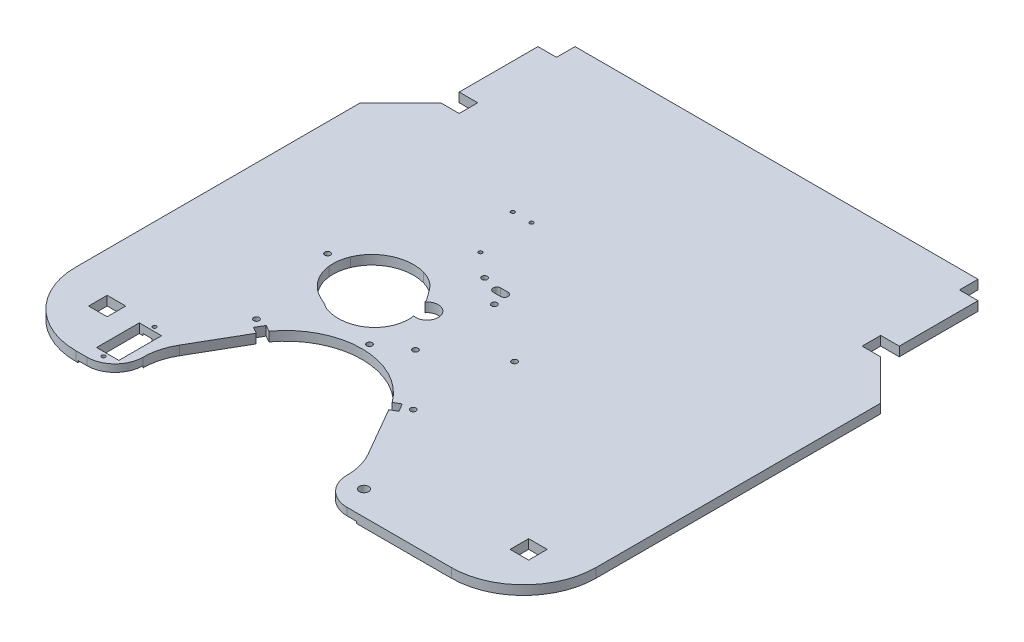
SolidWorks part; units mm, degrees
material "ABS PC"
ref_plane "Plan de face" through (0, 0, 0) normal (0, 0, 1) x (1, 0, 0)
ref_plane "Plan de dessus" through (0, 0, 0) normal (0, 1, 0) x (1, 0, 0)
ref_plane "Plan de droite" through (0, 0, 0) normal (1, 0, 0) x (0, 0, -1)
sketch "Esquisse1" plane through (0, 0, 0) normal (0, 1, 0) x (1, 0, 0)
  line L1 (-140.1, 31.2) -> (140.1, 31.2)
  line L2 (-140.1, 31.2) -> (-140.1, -245.0829)
  line L3 (-140.1, -245.0829) -> (140.1, -245.0829)
  line L4 (140.1, 31.2) -> (140.1, -245.0829)
  line L5 (45, -245.0829) -> (50, -245.0829) construction
  line L6 (-113.5, 31.2) -> (113.5, 31.2) construction
  line L7 (140.1, -4) -> (140.1, 4) construction
  line L8 (-140.1, 4) -> (-140.1, -4) construction
extrude "Boss.-Extru.1" add sketch "Esquisse1" along normal blind 5
sketch "Esquisse2" plane through (0, 0, 0) normal (0, 1, 0) x (1, 0, 0)
  line L3 (-58.1815, -184) -> (-61.6457, -182)
  line L4 (-61.6457, -182) -> (-64.1457, -186.3301)
  line L5 (-64.1457, -186.3301) -> (-60.6815, -188.3301)
  line L7 (-25, -132) -> (-25, -245.0829) construction
  line L8 (-58.1815, -184) -> (-60.6815, -188.3301) construction
  line L9 (-62.6323, -132) -> (62.6323, -132) construction
  line L10 (-25, -62.6323) -> (-25, 62.6323) construction
  line L11 (-60.6815, -188.3301) -> (-75.8539, -214.6094)
  line L13 (-58.1815, -184) -> (-54.7174, -186) construction
  line L14 (-25, -168.5125) -> (-25, -231.5125) construction
  line L16 (140.1, -245.0829) -> (-140.1, -245.0829) construction
  line L17 (-140.1, -245.0829) -> (140.1, -245.0829) construction
  line L18 (8.1815, -184) -> (4.7174, -186) construction
  line L20 (8.1815, -184) -> (10.6815, -188.3301) construction
  line L21 (10.6815, -188.3301) -> (25.8539, -214.6094)
  line L22 (14.1457, -186.3301) -> (10.6815, -188.3301)
  line L23 (11.6457, -182) -> (14.1457, -186.3301)
  line L24 (8.1815, -184) -> (11.6457, -182)
  line L25 (-62.8957, -184.1651) -> (-67.2258, -181.6651) construction
  line L26 (-95, -245.0829) -> (45, -245.0829)
  arc A1 (8.1815, -184) -> (-58.1815, -184) centre (-25, -208.0829) ccw
  arc A2 (-95, -245.0829) -> (-80, -230.0829) centre (-95, -230.0829) ccw
  arc A3 (-95, -245.0829) -> (-86.2863, -217.8734) centre (-95, -230.0829) ccw construction
  arc A4 (-80, -230.0829) -> (-75.8539, -214.6094) centre (-49.0531, -230.0829) cw
  arc A5 (30, -230.0829) -> (25.8539, -214.6094) centre (-0.9469, -230.0829) ccw
  arc A6 (45, -245.0829) -> (30, -230.0829) centre (45, -230.0829) cw
  circle A8 centre (-67.2258, -181.6651) radius 1.5
  circle A10 centre (17.2258, -181.6651) radius 1.5
  dimension "D4" = 41
  dimension "D8" = 5
  dimension "D9" = 3
  dimension "D1" = 4
  dimension "D2" = 52
  dimension "D3" = 37
  dimension "D5" = 90
  dimension "D6" = 5
  dimension "D7" = 30
extrude "Enlèv. mat.-Extru.2" cut sketch "Esquisse2" along normal through all
sketch "Esquisse3" plane through (0, 5, 0) normal (0, 1, 0) x (1, 0, 0)
  line L0 (-30.2322, -127.0569) -> (-26.1247, -139.1312)
  spline S0 degree 3 poles (-1524.8341, -1452.5331) (-200.5452, -428.348) (10.8704, -188.1918) (-31.7245, -126.6315) (-31.8941, -126.3945) (-32.4016, -125.6823) (-32.7422, -125.2091) (-58.8228, -89.2587) (-90.5389, -57.2295) (-1659.8243, -1285.8652) knots -31.850463 -31.850463 -31.850463 -31.850463 0.125 0.125 0.25 0.25 0.5 0.5 19.29405 19.29405 19.29405 19.29405 only from (-31.0727, -127.5986) to (-35.1803, -121.9365)
  spline S1 degree 3 poles (364.0931, 1835.8687) (-340.6814, -513.038) (-113.9465, -84.5198) (-40.8811, -117.114) (-40.044, -117.5631) (-38.8602, -118.3319) (-38.4767, -118.6044) (-37.7343, -119.185) (-37.3745, -119.4945) (-14.0434, -142.3698) (-68.5996, -233.8683) (1519.3139, 1134.9781) knots -20.904049 -20.904049 -20.904049 -20.904049 0.25 0.25 0.5 0.5 0.625 0.625 0.75 0.75 9.313235 9.313235 9.313235 9.313235 only from (-44.3577, -115.7789) to (-35.1803, -121.9365)
  spline S2 degree 3 poles (-1305.5548, -1643.1059) (8.9079, -543.4216) (30.3671, -122.9167) (-49.4488, -114.9227) (-50.737, -114.9092) (-52.6603, -115.0546) (-53.2999, -115.1309) (-54.576, -115.34) (-55.2153, -115.474) (-57.0956, -115.9555) (-58.3066, -116.3821) (-60.0589, -117.1815) (-60.6325, -117.4741) (-61.7574, -118.1146) (-62.3096, -118.4643) (-63.8985, -119.5739) (-64.8782, -120.402) (-66.225, -121.7806) (-66.6531, -122.2633) (-67.2625, -123.0236) (-67.4604, -123.2834) (-67.8414, -123.8087) (-68.025, -124.075) (-110.7871, -189.31) (235.2262, -459.8979) (1576.8374, -1257.2957) knots -7.457247 -7.457247 -7.457247 -7.457247 0.125 0.125 0.25 0.25 0.3125 0.3125 0.375 0.375 0.5 0.5 0.5625 0.5625 0.625 0.625 0.75 0.75 0.8125 0.8125 0.84375 0.84375 0.875 0.875 8.398041 8.398041 8.398041 8.398041 only from (-44.3577, -115.7789) to (-70, -127.755)
  spline S3 degree 3 poles (-47.9813, 1856.8275) (125.181, -244.0769) (-72.0855, -184.256) (-71.4642, -134.1161) (-71.4011, -133.3001) (-71.1736, -131.6775) (-71.0075, -130.8697) (-17.8642, 63.8002) (2969.019, -622.8948) (-1651.8454, 973.7425) knots -14.76961 -14.76961 -14.76961 -14.76961 0.25 0.25 0.5 0.5 0.75 0.75 62.135828 62.135828 62.135828 62.135828 only from (-71.343, -137.3985) to (-70, -127.755)
  spline S4 degree 3 poles (-2001.2881, 32.8008) (2629.6596, 821.1196) (-125.1007, 42.2047) (-70.5251, -141.1324) (-70.3458, -141.6526) (-69.9413, -142.6832) (-69.718, -143.1876) (-68.9919, -144.665) (-68.4298, -145.6034) (-67.479, -146.9469) (-67.1435, -147.384) (-66.4359, -148.235) (-66.0677, -148.6441) (-64.924, -149.8269) (-64.1096, -150.5562) (-62.7975, -151.5474) (-62.3475, -151.8633) (-61.6568, -152.3195) (-61.425, -152.47) (-60.9583, -152.7645) (-60.7209, -152.9041) (-60.001, -153.3084) (-59.5102, -153.5575) (-58.5114, -154.0234) (-58.0032, -154.2398) (-57.2409, -154.5624) (-56.9867, -154.6699) (-56.4801, -154.8889) (-56.2268, -154.9985) (-55.7258, -155.2315) (-55.4826, -155.3662) (-43.6824, -163.0213) (-44.4169, -201.2221) (725.64, 1684.5228) knots -21.636057 -21.636057 -21.636057 -21.636057 0.125 0.125 0.1875 0.1875 0.25 0.25 0.375 0.375 0.4375 0.4375 0.5 0.5 0.625 0.625 0.6875 0.6875 0.71875 0.71875 0.75 0.75 0.8125 0.8125 0.875 0.875 0.90625 0.90625 0.9375 0.9375 0.96875 0.96875 2.500832 2.500832 2.500832 2.500832 only from (-71.343, -137.3985) to (-54.5478, -156)
  spline S5 degree 3 poles (-1738.4139, 892.0597) (140.9741, 43.0874) (2.9113, -175.9233) (-52.26, -157.2053) (-52.4819, -157.1257) (-52.8129, -157.0004) (-52.9231, -156.9582) (-53.1393, -156.8624) (-53.2451, -156.8096) (-53.557, -156.6406) (-53.7605, -156.5209) (-66.1987, -148.6858) (-58.0496, -108.9252) (-1163.5294, -1819.9055) knots -30.265211 -30.265211 -30.265211 -30.265211 0.5 0.5 0.625 0.625 0.6875 0.6875 0.75 0.75 0.875 0.875 8.537384 8.537384 8.537384 8.537384 only from (-49.3008, -158) to (-54.5478, -156)
  spline S6 degree 3 poles (-1949.1275, 426.9773) (43.5324, -0.0898) (1.2961, -154.0463) (-44.2435, -158.3269) (-44.8765, -158.3561) (-46.1445, -158.356) (-46.7811, -158.3264) (-118.6227, -151.5571) (-143.9564, 223.9249) (-15.0957, 1838.9163) knots -17.515041 -17.515041 -17.515041 -17.515041 0.25 0.25 0.5 0.5 0.75 0.75 28.888572 28.888572 28.888572 28.888572 only from (-41.7229, -158) to (-49.3008, -158)
  spline S7 degree 3 poles (-1666.5719, -1296.3963) (-65.6297, 95.6251) (7.8642, -129.1094) (-36.0016, -155.9655) (-36.6799, -156.3213) (-38.0707, -156.9471) (-38.7813, -157.2165) (-86.4686, -172.17) (-201.3678, -13.098) (1712.2684, 789.9411) knots -16.36827 -16.36827 -16.36827 -16.36827 0.25 0.25 0.5 0.5 0.75 0.75 16.93969 16.93969 16.93969 16.93969 only from (-33.4851, -154.245) to (-41.7229, -158)
  spline S8 degree 3 poles (1046.2165, -1823.3231) (-784.0739, 385.5367) (-101.1747, -227.9262) (-31.3895, -152.2364) (-31.1171, -151.9192) (-30.5932, -151.2613) (-30.343, -150.9217) (-29.6368, -149.8847) (-29.2193, -149.1653) (-28.6747, -148.043) (-28.5063, -147.6619) (-15.3248, -114.6524) (-97.8799, -22.7511) (-912.2607, -1937.4947) knots -30.529041 -30.529041 -30.529041 -30.529041 0.25 0.25 0.375 0.375 0.5 0.5 0.75 0.75 0.875 0.875 11.380924 11.380924 11.380924 11.380924 only from (-33.4851, -154.245) to (-27.928, -146.0877)
  spline S9 degree 3 poles (-89.1423, -2133.2638) (-210.1557, -2.8223) (-21.556, -93.2311) (-33.3079, -196.0579) (-262.9799, -213.9602) (-2020.0373, 10.4615) knots -20.97712 -20.97712 -20.97712 -20.97712 0.5 0.5 23.678782 23.678782 23.678782 23.678782 only from (-27.1228, -139.1933) to (-27.928, -146.0877)
  spline S10 degree 3 poles (-27.1228, -139.1933) (-27.0502, -140.3605) (-27.0765, -141.534) (-27.3396, -143.8367) (-27.5752, -144.9715) (-27.928, -146.0877) knots 0 0 0 0 0.5 0.5 1 1 1 1 construction
  spline S11 degree 3 poles (-33.4851, -154.245) (-32.8413, -153.7217) (-32.2363, -153.1548) (-31.3895, -152.2364) (-31.1171, -151.9192) (-30.5932, -151.2613) (-30.343, -150.9217) (-29.6368, -149.8847) (-29.2193, -149.1653) (-28.6747, -148.043) (-28.5063, -147.6619) (-28.1963, -146.8857) (-28.0548, -146.4892) (-27.928, -146.0877) knots 0 0 0 0 0.25 0.25 0.375 0.375 0.5 0.5 0.75 0.75 0.875 0.875 1 1 1 1 construction
  spline S12 degree 3 poles (-33.4851, -154.245) (-34.0776, -154.7266) (-34.7013, -155.1695) (-36.0016, -155.9655) (-36.6799, -156.3213) (-38.0707, -156.9471) (-38.7813, -157.2165) (-40.2317, -157.6713) (-40.9731, -157.8572) (-41.7229, -158) knots 0 0 0 0 0.25 0.25 0.5 0.5 0.75 0.75 1 1 1 1 construction
  spline S13 degree 3 poles (-41.7229, -158) (-42.3482, -158.1191) (-42.9796, -158.2081) (-44.2435, -158.3269) (-44.8765, -158.3561) (-46.1445, -158.356) (-46.7811, -158.3264) (-48.0464, -158.2072) (-48.6755, -158.1184) (-49.3008, -158) knots 0 0 0 0 0.25 0.25 0.5 0.5 0.75 0.75 1 1 1 1 construction
  spline S14 degree 3 poles (-49.3008, -158) (-50.2287, -157.8243) (-51.1437, -157.584) (-52.26, -157.2053) (-52.4819, -157.1257) (-52.8129, -157.0004) (-52.9231, -156.9582) (-53.1393, -156.8624) (-53.2451, -156.8096) (-53.557, -156.6406) (-53.7605, -156.5209) (-54.1598, -156.2694) (-54.3541, -156.1351) (-54.5478, -156) knots 0 0 0 0 0.5 0.5 0.625 0.625 0.6875 0.6875 0.75 0.75 0.875 0.875 1 1 1 1 construction
  spline S15 degree 3 poles (-71.343, -137.3985) (-71.2139, -138.4875) (-70.994, -139.5573) (-70.5251, -141.1324) (-70.3458, -141.6526) (-69.9413, -142.6832) (-69.718, -143.1876) (-68.9919, -144.665) (-68.4298, -145.6034) (-67.479, -146.9469) (-67.1435, -147.384) (-66.4359, -148.235) (-66.0677, -148.6441) (-64.924, -149.8269) (-64.1096, -150.5562) (-62.7975, -151.5474) (-62.3475, -151.8633) (-61.6568, -152.3195) (-61.425, -152.47) (-60.9583, -152.7645) (-60.7209, -152.9041) (-60.001, -153.3084) (-59.5102, -153.5575) (-58.5114, -154.0234) (-58.0032, -154.2398) (-57.2409, -154.5624) (-56.9867, -154.6699) (-56.4801, -154.8889) (-56.2268, -154.9985) (-55.7258, -155.2315) (-55.4826, -155.3662) (-55.0108, -155.6722) (-54.7801, -155.838) (-54.5478, -156) knots 0 0 0 0 0.125 0.125 0.1875 0.1875 0.25 0.25 0.375 0.375 0.4375 0.4375 0.5 0.5 0.625 0.625 0.6875 0.6875 0.71875 0.71875 0.75 0.75 0.8125 0.8125 0.875 0.875 0.90625 0.90625 0.9375 0.9375 0.96875 0.96875 1 1 1 1 construction
  spline S16 degree 3 poles (-71.343, -137.3985) (-71.4399, -136.5817) (-71.4845, -135.7579) (-71.4642, -134.1161) (-71.4011, -133.3001) (-71.1736, -131.6775) (-71.0075, -130.8697) (-70.5764, -129.2906) (-70.3122, -128.5156) (-70, -127.755) knots 0 0 0 0 0.25 0.25 0.5 0.5 0.75 0.75 1 1 1 1 construction
  spline S17 degree 3 poles (-44.3577, -115.7789) (-45.5925, -115.4238) (-46.8598, -115.182) (-49.4488, -114.9227) (-50.737, -114.9092) (-52.6603, -115.0546) (-53.2999, -115.1309) (-54.576, -115.34) (-55.2153, -115.474) (-57.0956, -115.9555) (-58.3066, -116.3821) (-60.0589, -117.1815) (-60.6325, -117.4741) (-61.7574, -118.1146) (-62.3096, -118.4643) (-63.8985, -119.5739) (-64.8782, -120.402) (-66.225, -121.7806) (-66.6531, -122.2633) (-67.2625, -123.0236) (-67.4604, -123.2834) (-67.8414, -123.8087) (-68.025, -124.075) (-68.9095, -125.4243) (-69.5098, -126.5605) (-70, -127.755) knots 0 0 0 0 0.125 0.125 0.25 0.25 0.3125 0.3125 0.375 0.375 0.5 0.5 0.5625 0.5625 0.625 0.625 0.75 0.75 0.8125 0.8125 0.84375 0.84375 0.875 0.875 1 1 1 1 construction
  spline S18 degree 3 poles (-44.3577, -115.7789) (-43.4629, -116.0363) (-42.5879, -116.3526) (-40.8811, -117.114) (-40.044, -117.5631) (-38.8602, -118.3319) (-38.4767, -118.6044) (-37.7343, -119.185) (-37.3745, -119.4945) (-36.3675, -120.4818) (-35.7623, -121.1988) (-35.1803, -121.9365) knots 0 0 0 0 0.25 0.25 0.5 0.5 0.625 0.625 0.75 0.75 1 1 1 1 construction
  spline S19 degree 3 poles (-31.0727, -127.5986) (-31.2308, -127.3534) (-31.3928, -127.111) (-31.7245, -126.6315) (-31.8941, -126.3945) (-32.4016, -125.6823) (-32.7422, -125.2091) (-33.7693, -123.7933) (-34.4583, -122.8518) (-35.1803, -121.9365) knots 0 0 0 0 0.125 0.125 0.25 0.25 0.5 0.5 1 1 1 1 construction
  spline S20 degree 1 poles (-26.1247, -139.1312) (-26.9745, -146.389) knots 0 0 1 1 construction
  spline S21 degree 1 poles (-32.8544, -155.021) (-26.9745, -146.389) knots 0 0 1 1 construction
  spline S22 degree 1 poles (-32.8544, -155.021) (-41.5359, -158.9824) knots 0 0 1 1 construction
  spline S23 degree 1 poles (-41.5359, -158.9824) (-49.4869, -158.9825) knots 0 0 1 1 construction
  spline S24 degree 1 poles (-49.4869, -158.9825) (-55.1198, -156.8203) knots 0 0 1 1 construction
  spline S25 degree 1 poles (-72.336, -137.5162) (-55.1198, -156.8203) knots 0 0 1 1 construction
  spline S26 degree 1 poles (-72.336, -137.5162) (-70.9251, -127.3753) knots 0 0 1 1 construction
  spline S27 degree 1 poles (-44.0813, -114.8179) (-70.9251, -127.3753) knots 0 0 1 1 construction
  spline S28 degree 1 poles (-44.0813, -114.8179) (-34.3952, -121.3172) knots 0 0 1 1 construction
  spline S29 degree 1 poles (-30.2322, -127.0569) (-34.3952, -121.3172) knots 0 0 1 1 construction
  spline S30 degree 3 poles (-26.1247, -139.1312) (-25.9734, -141.5623) (-26.2405, -144.0664) (-26.9745, -146.389) knots 0 0 0 0 1 1 1 1
  spline S31 degree 3 poles (-26.9745, -146.389) (-27.2409, -147.2323) (-27.9017, -148.8872) (-29.2221, -151.1686) (-30.8961, -153.272) (-32.1739, -154.4679) (-32.8544, -155.021) knots 0 0 0 0 0.25 0.5 0.75 1 1 1 1
  spline S32 degree 3 poles (-32.8544, -155.021) (-34.1022, -156.0352) (-36.8953, -157.7328) (-39.967, -158.6836) (-41.5359, -158.9824) knots 0 0 0 0 0.5 1 1 1 1
  spline S33 degree 3 poles (-41.5359, -158.9824) (-44.1394, -159.4781) (-46.8829, -159.4757) (-49.4869, -158.9825) knots 0 0 0 0 1 1 1 1
  spline S34 degree 3 poles (-49.4869, -158.9825) (-49.9734, -158.8904) (-50.9415, -158.6718) (-52.0056, -158.3522) (-52.7107, -158.1061) (-53.0491, -157.981) (-53.4323, -157.8343) (-53.8396, -157.6291) (-54.1621, -157.4443) (-54.4936, -157.2441) (-54.8226, -157.0271) (-55.0192, -156.8904) (-55.1198, -156.8203) knots 0 0 0 0 0.25 0.5 0.5625 0.625 0.6875 0.75 0.8125 0.875 0.9375 1 1 1 1
  spline S35 degree 3 poles (-55.1198, -156.8203) (-55.3426, -156.6649) (-55.8212, -156.3208) (-56.3578, -156.0288) (-57.1358, -155.6943) (-58.1278, -155.2724) (-59.4415, -154.7137) (-60.7152, -154.07) (-61.7361, -153.4634) (-62.6711, -152.8531) (-64.3255, -151.7044) (-66.4613, -149.7979) (-68.6889, -147.1234) (-71.0457, -143.1846) (-72.0656, -139.797) (-72.336, -137.5162) knots 0 0 0 0 0.03125 0.0625 0.09375 0.125 0.1875 0.25 0.28125 0.3125 0.375 0.5 0.625 0.75 1 1 1 1
  spline S36 degree 3 poles (-72.336, -137.5162) (-72.5389, -135.806) (-72.4971, -132.3145) (-71.5776, -128.965) (-70.9251, -127.3753) knots 0 0 0 0 0.5 1 1 1 1
  spline S37 degree 3 poles (-70.9251, -127.3753) (-70.4131, -126.1277) (-69.1525, -123.7337) (-66.5762, -120.5203) (-63.4912, -117.9189) (-59.9299, -115.8897) (-56.1282, -114.5536) (-52.0981, -113.8904) (-48.0468, -113.9388) (-45.3772, -114.4451) (-44.0813, -114.8179) knots 0 0 0 0 0.125 0.25 0.375 0.5 0.625 0.75 0.875 1 1 1 1
  spline S38 degree 3 poles (-44.0813, -114.8179) (-43.1424, -115.0879) (-41.3106, -115.748) (-39.1035, -116.9336) (-37.4821, -118.0811) (-36.3107, -119.0968) (-35.3076, -120.1888) (-34.6959, -120.936) (-34.3952, -121.3172) knots 0 0 0 0 0.25 0.5 0.625 0.75 0.875 1 1 1 1
  spline S39 degree 3 poles (-34.3952, -121.3172) (-33.6647, -122.2432) (-32.6101, -123.6823) (-31.2535, -125.565) (-30.5565, -126.5538) (-30.2322, -127.0569) knots 0 0 0 0 0.5 0.75 1 1 1 1
  dimension "D1" = 1
extrude "Enlèv. mat.-Extru.3" cut sketch "Esquisse3" against normal through all
sketch "Esquisse4" plane through (0, 5, 0) normal (0, 1, 0) x (1, 0, 0)
  circle A0 centre (-48.2, -62.65) radius 1
  circle A1 centre (-38.1, -62.65) radius 1
  circle A2 centre (-38.1, -90.25) radius 1
  dimension "D1" = 2
extrude "Enlèv. mat.-Extru.4" cut sketch "Esquisse4" against normal through all
sketch "Esquisse5" plane through (0, 5, 0) normal (0, 1, 0) x (1, 0, 0)
  circle A0 centre (22.1224, -132) radius 1.5
  circle A1 centre (-10.0508, -153.25) radius 1.5
  circle A2 centre (-25, -163) radius 1.5
  circle A3 centre (-10.0508, -110.75) radius 1.5
  circle A4 centre (-25, -101) radius 1.5
  circle A5 centre (-78.6, -132) radius 1.5
  dimension "D1" = 3
extrude "Enlèv. mat.-Extru.5" cut sketch "Esquisse5" against normal through all
sketch "Esquisse6" plane through (0, 5, 0) normal (0, 1, 0) x (1, 0, 0)
  circle A0 centre (-25, -132) radius 6
  circle A1 centre (-25, -132) radius 5.4 construction
  dimension "D1" = 12
extrude "Enlèv. mat.-Extru.6" cut sketch "Esquisse6" against normal through all
sketch "Esquisse7" plane through (0, 5, 0) normal (0, 1, 0) x (1, 0, 0)
  line L1 (-16, -103.4) -> (-12, -103.4) construction
  line L2 (-16, -101.4) -> (-12, -101.4)
  line L3 (-16, -105.4) -> (-12, -105.4)
  arc A0 (-16, -101.4) -> (-16, -105.4) centre (-16, -103.4) ccw
  arc A6 (-12, -105.4) -> (-12, -101.4) centre (-12, -103.4) ccw
  arc A7 (-11.4091, -103.2958) -> (-12.5909, -103.2958) centre (-12, -103.4) ccw construction
  arc A9 (-15.4091, -103.2958) -> (-16.5909, -103.2958) centre (-16, -103.4) ccw construction
  point P2 (-14, -103.4)
  dimension "D1" = 4
extrude "Enlèv. mat.-Extru.7" cut sketch "Esquisse7" against normal through all
sketch "Esquisse8" plane through (0, 5, 0) normal (0, 1, 0) x (1, 0, 0)
  line L0 (140.1, -245.0829) -> (140.1, 31.2) construction
  line L1 (101.1, -245.0829) -> (140.1, -245.0829)
  line L2 (140.1, -245.0829) -> (140.1, -206.0829)
  line L3 (-140.1, -245.0829) -> (-140.1, -206.0829)
  line L4 (-140.1, 31.2) -> (-140.1, -245.0829) construction
  line L5 (-140.1, -245.0829) -> (-95, -245.0829) construction
  line L6 (-101.1, -245.0829) -> (-140.1, -245.0829)
  arc A0 (140.1, -206.0829) -> (101.1, -245.0829) centre (101.1, -206.0829) cw
  arc A1 (-140.1, -206.0829) -> (-101.1, -245.0829) centre (-101.1, -206.0829) ccw
extrude "Enlèv. mat.-Extru.8" cut sketch "Esquisse8" against normal through all
sketch "Esquisse9" plane through (0, 5, 0) normal (0, 1, 0) x (1, 0, 0)
  line L0 (-108.5, 21.2) -> (-118.5, 21.2) construction
  line L1 (-108.5, 21.2) -> (-108.5, 31.2) construction
  line L2 (-108.5, -31.2) -> (-108.5, -21.2) construction
  line L3 (-108.5, -21.2) -> (-118.5, -21.2) construction
  line L4 (-108.5, -31.2) -> (-118.5, -31.2) construction
  line L5 (-108.5, 21.2) -> (-118.5, 21.2)
  line L6 (-108.5, 21.2) -> (-108.5, 31.2)
  line L7 (-108.5, -31.2) -> (-108.5, -21.2)
  line L8 (-108.5, -21.2) -> (-118.5, -21.2)
  line L9 (-108.5, -31.2) -> (-118.5, -31.2)
  line L10 (-118.5, -21.2) -> (-118.5, 21.2)
  line L11 (-118.5, -31.2) -> (-140.1, -52.8)
  line L12 (-140.1, 31.2) -> (-140.1, -206.0829) construction
  line L13 (-140.1, -52.8) -> (-140.1, 31.2)
  line L14 (-140.1, 31.2) -> (-108.5, 31.2)
  line L15 (0, 0) -> (0, 79.4635) construction
  line L16 (140.1, 31.2) -> (108.5, 31.2)
  line L17 (140.1, -52.8) -> (140.1, 31.2)
  line L18 (118.5, -31.2) -> (140.1, -52.8)
  line L19 (118.5, -21.2) -> (118.5, 21.2)
  line L20 (108.5, -31.2) -> (118.5, -31.2)
  line L21 (108.5, -21.2) -> (118.5, -21.2)
  line L22 (108.5, -31.2) -> (108.5, -21.2)
  line L23 (108.5, 21.2) -> (108.5, 31.2)
  line L24 (108.5, 21.2) -> (118.5, 21.2)
  dimension "D1" = 45
extrude "Enlèv. mat.-Extru.9" cut sketch "Esquisse9" against normal through all
sketch "Esquisse10" plane through (0, 0, 0) normal (0, -1, 0) x (1, 0, 0)
  line L1 (50, 242.0829) -> (50, 245.0829) construction
  line L2 (50, 245.0829) -> (45, 245.0829) construction
  line L3 (45, 242.0829) -> (50, 242.0829) construction
  line L5 (50, 242.0829) -> (50, 245.0829)
  line L6 (50, 245.0829) -> (45, 245.0829)
  line L7 (45, 242.0829) -> (50, 242.0829)
  line L9 (-88.029, 220.3153) -> (-86.2863, 217.8734)
  line L10 (-95, 245.0829) -> (-95, 242.0829)
  line L15 (-95, 242.0829) -> (-95, 245.0829)
  line L16 (-95, 245.0829) -> (-100, 245.0829)
  line L17 (-100, 245.0829) -> (-100, 242.0829)
  line L18 (-100, 242.0829) -> (-95, 242.0829)
  line L20 (-95, 245.0829) -> (-100, 245.0829)
  line L21 (-100, 245.0829) -> (-100, 242.0829)
  line L22 (-100, 242.0829) -> (-95, 242.0829)
  arc A0 (-88.029, 220.3153) -> (-25, 23.5) centre (-25, 132) ccw construction
  arc A1 (-86.2863, 217.8734) -> (-25, 26.5) centre (-25, 132) ccw construction
  arc A2 (-25, 26.5) -> (36.2863, 217.8734) centre (-25, 132) ccw construction
  arc A3 (-25, 23.5) -> (38.029, 220.3153) centre (-25, 132) ccw construction
  arc A4 (-88.029, 220.3153) -> (-25, 23.5) centre (-25, 132) ccw
  arc A5 (-86.2863, 217.8734) -> (-25, 26.5) centre (-25, 132) ccw
  arc A6 (-25, 26.5) -> (36.2863, 217.8734) centre (-25, 132) ccw
  arc A7 (-25, 23.5) -> (38.029, 220.3153) centre (-25, 132) ccw
  arc A8 (45, 245.0829) -> (36.2863, 217.8734) centre (45, 230.0829) ccw construction
  arc A9 (45, 242.0829) -> (38.029, 220.3153) centre (45, 230.0829) ccw construction
  arc A10 (45, 245.0829) -> (36.2863, 217.8734) centre (45, 230.0829) ccw
  arc A11 (45, 242.0829) -> (38.029, 220.3153) centre (45, 230.0829) ccw
  arc A14 (-86.2863, 217.8734) -> (-95, 245.0829) centre (-95, 230.0829) ccw
  arc A15 (-88.029, 220.3153) -> (-95, 242.0829) centre (-95, 230.0829) ccw
  arc A16 (-86.2863, 217.8734) -> (-95, 245.0829) centre (-95, 230.0829) ccw
  arc A17 (-88.029, 220.3153) -> (-95, 242.0829) centre (-95, 230.0829) ccw
  dimension "D1" = 0
  dimension "D2" = 0
extrude "Enlèv. mat.-Extru.10" cut sketch "Esquisse10" against normal blind 1
sketch "Esquisse11" plane through (0, 5, 0) normal (0, 1, 0) x (1, 0, 0)
  line L4 (-118.5, -210.8) -> (-118.5, -220.8)
  line L5 (-108.5, -210.8) -> (-118.5, -210.8)
  line L6 (-108.5, -220.8) -> (-108.5, -210.8)
  line L7 (-118.5, -220.8) -> (-108.5, -220.8)
  line L8 (-118.5, -210.8) -> (-118.5, -220.8)
  line L9 (-108.5, -210.8) -> (-118.5, -210.8)
  line L10 (-108.5, -220.8) -> (-108.5, -210.8)
  line L11 (-118.5, -220.8) -> (-108.5, -220.8)
  line L12 (108.5, -210.8) -> (108.5, -220.8)
  line L13 (118.5, -210.8) -> (108.5, -210.8)
  line L14 (118.5, -220.8) -> (118.5, -210.8)
  line L15 (108.5, -220.8) -> (118.5, -220.8)
  line L16 (108.5, -210.8) -> (108.5, -220.8)
  line L17 (118.5, -210.8) -> (108.5, -210.8)
  line L18 (118.5, -220.8) -> (118.5, -210.8)
  line L19 (108.5, -220.8) -> (118.5, -220.8)
  dimension "D1" = 0
  dimension "D2" = 0
extrude "Enlèv. mat.-Extru.11" cut sketch "Esquisse11" against normal through all
sketch "Esquisse12" plane through (0, 5, 0) normal (0, 1, 0) x (1, 0, 0)
  line L4 (-97, -215) -> (-97, -238)
  line L5 (-97, -238) -> (-85, -238)
  line L6 (-85, -238) -> (-85, -215)
  line L7 (-85, -215) -> (-97, -215)
  line L8 (-97, -215) -> (-97, -238)
  line L9 (-97, -238) -> (-85, -238)
  line L10 (-85, -238) -> (-85, -215)
  line L11 (-85, -215) -> (-97, -215)
  circle A0 centre (41, -232) radius 2.5 construction
  circle A1 centre (41, -232) radius 2.5
  circle A2 centre (-91, -212.75) radius 1
  circle A3 centre (-91, -240.25) radius 1
  dimension "D2" = 2
  dimension "D1" = 0
extrude "Enlèv. mat.-Extru.12" cut sketch "Esquisse12" against normal through all
